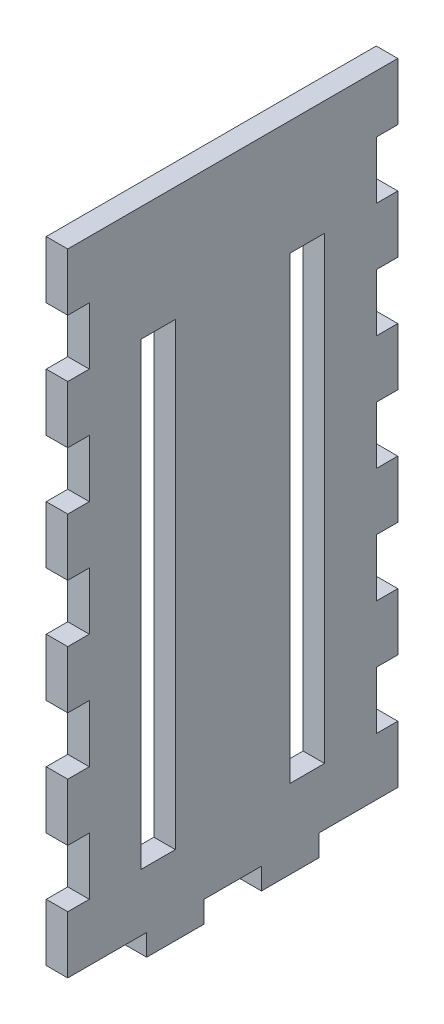
SolidWorks part; units mm, degrees
ref_plane "Front Plane" through (0, 0, 0) normal (0, 0, 1) x (1, 0, 0)
ref_plane "Top Plane" through (0, 0, 0) normal (0, 1, 0) x (1, 0, 0)
ref_plane "Right Plane" through (0, 0, 0) normal (1, 0, 0) x (0, 0, -1)
sketch "Sketch1" plane through (0, 0, 0) normal (1, 0, 0) x (0, 0, -1)
  line L1 (-63.5, -139.7) -> (63.5, -139.7)
  line L2 (-63.5, -139.7) -> (-63.5, 139.7)
  line L3 (-63.5, 139.7) -> (63.5, 139.7)
  line L4 (63.5, -139.7) -> (63.5, 139.7)
  line L5 (-63.5, -139.7) -> (63.5, 139.7) construction
  line L6 (-63.5, 139.7) -> (63.5, -139.7) construction
  point P0 (0, 0)
  dimension "D1" = 127
  dimension "D2" = 279.4
extrude "Boss-Extrude1" add sketch "Sketch1" along normal blind 9.525
sketch "Sketch2" plane through (0, 0, 63.5) normal (0, 0, 1) x (1, 0, 0)
  line L0 (0, 139.7) -> (0, -139.7) construction
  line L1 (0, 139.7) -> (9.525, 139.7)
  line L2 (0, 139.7) -> (0, 114.3)
  line L3 (0, 114.3) -> (9.525, 114.3)
  line L4 (9.525, 139.7) -> (9.525, 114.3)
  line L5 (0, -69.85) -> (0, 69.85) construction
  line L6 (9.525, 139.7) -> (9.525, -139.7) construction
  line L7 (9.525, 139.7) -> (0, 139.7) construction
  dimension "D1" = 25.4
  dimension "D2" = 0
extrude "Boss-Extrude2" add sketch "Sketch2" along normal blind 9.525
pattern_linear "LPattern1" count 6 spacing 50.8 along (0, -1, 0) of "Boss-Extrude2"
mirror "Mirror1" about plane through (0, 0, 0) normal (0, 0, 1) of "LPattern1"
sketch "Sketch3" plane through (0, -139.7, 0) normal (0, -1, 0) x (1, 0, 0)
  line L0 (0, 73.025) -> (0, -73.025) construction
  line L1 (0, 38.1) -> (9.525, 38.1)
  line L2 (0, 38.1) -> (0, 12.7)
  line L3 (0, 12.7) -> (9.525, 12.7)
  line L4 (9.525, 38.1) -> (9.525, 12.7)
  line L5 (9.525, 73.025) -> (9.525, -73.025) construction
  line L6 (0, 73.025) -> (9.525, 73.025) construction
  dimension "D1" = 34.925
  dimension "D2" = 25.4
extrude "Boss-Extrude3" add sketch "Sketch3" along normal blind 9.525
pattern_linear "LPattern2" count 2 spacing 50.8 along (0, 0, -1) of "Boss-Extrude3"
sketch "Sketch4" plane through (9.525, 0, 0) normal (1, 0, 0) x (0, 0, -1)
  line L1 (-40.64, -114.3) -> (-25.4, -114.3)
  line L3 (-40.64, 88.9) -> (-25.4, 88.9)
  line L5 (-73.025, -139.7) -> (-38.1, -139.7) construction
  line L6 (-73.025, 88.9) -> (-63.5, 88.9) construction
  line L7 (-25.4, -114.3) -> (-25.4, 88.9)
  line L8 (-40.64, -114.3) -> (-40.64, 88.9)
  line L9 (0, -139.7) -> (0, 139.7) construction
  line L10 (-12.7, -139.7) -> (12.7, -139.7) construction
  line L11 (73.025, 139.7) -> (-73.025, 139.7) construction
  point P10 (-68.2625, 88.9)
  dimension "D1" = 25.4
  dimension "D2" = 15.24
  dimension "D3" = 25.4
  dimension "D4" = 0
extrude "Cut-Extrude1" cut sketch "Sketch4" against normal blind 9.525
mirror "Mirror2" about plane through (0, 0, 0) normal (0, 0, 1) of "Cut-Extrude1"
